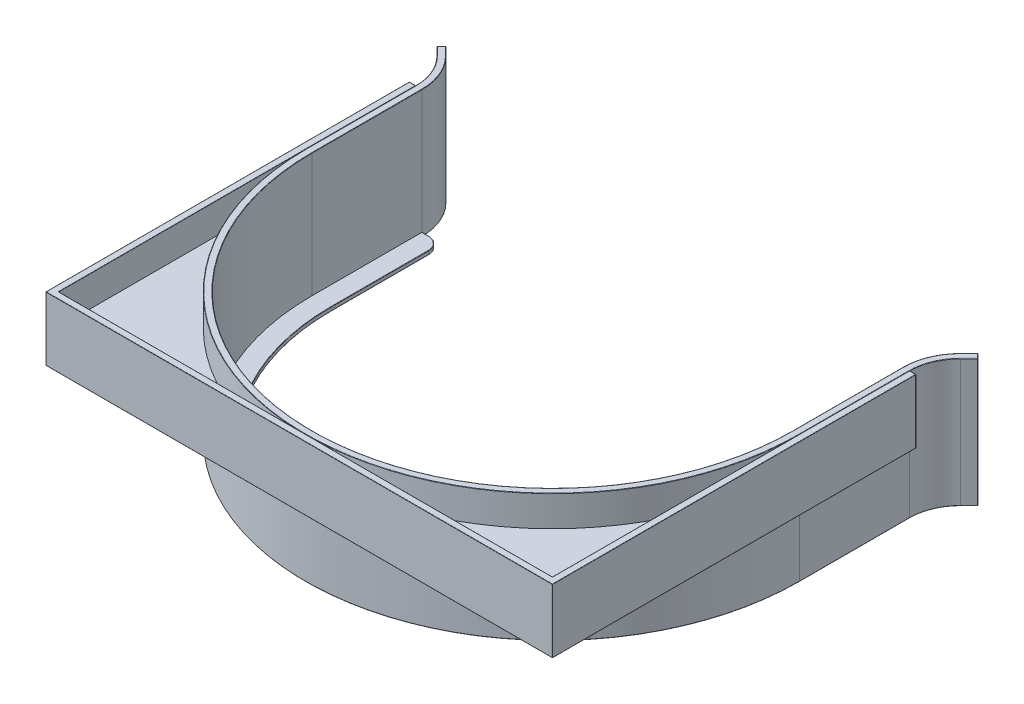
SolidWorks part; units mm, degrees
material "1060 Alloy"
ref_plane "Front Plane" through (0, 0, 0) normal (0, 0, 1) x (1, 0, 0)
ref_plane "Top Plane" through (0, 0, 0) normal (0, 1, 0) x (1, 0, 0)
ref_plane "Right Plane" through (0, 0, 0) normal (1, 0, 0) x (0, 0, -1)
sketch "Sketch1" plane through (0, 0, 0) normal (0, 1, 0) x (1, 0, 0)
  line L8 (193.5, 0) -> (188.5, 0)
  line L9 (-193.5, 0) -> (-188.5, 0)
  arc A0 (-188.5, 0) -> (188.5, 0) centre (0, 0) ccw
  arc A1 (-193.5, 0) -> (193.5, 0) centre (0, 0) ccw
  circle A2 centre (0, 0) radius 193.5 construction
  circle A3 centre (0, 0) radius 188.5 construction
  dimension "D1" = 377
  dimension "D2" = 5
extrude "Boss-Extrude1" add sketch "Sketch1" along normal blind 100 contours A1 L8 A0 L9 region at (0, 0, 189.1732)
sketch "Sketch2" plane through (0, 0, 0) normal (0, 1, 0) x (1, 0, 0)
  line L0 (-212.0355, 121.4645) -> (-205.2157, 114.6447)
  line L1 (-212.0355, 121.4645) -> (-208.5, 125)
  line L2 (-208.5, 125) -> (-201.6802, 118.1802)
  line L3 (-193.5, 86.3604) -> (-193.5, 0)
  line L4 (-188.5, 0) -> (-188.5, 86.3604)
  line L5 (-188.5, 0) -> (-193.5, 0)
  arc A0 (-205.2157, 114.6447) -> (-193.5, 86.3604) centre (-233.5, 86.3604) cw
  arc A2 (-201.6802, 118.1802) -> (-188.5, 86.3604) centre (-233.5, 86.3604) cw
  arc A5 (-193.5, 0) -> (193.5, 0) centre (0, 0) ccw construction
  dimension "D4" = 135
  dimension "D3" = 40
  dimension "D2" = 125
  dimension "D1" = 20
extrude "Boss-Extrude2" add sketch "Sketch2" along normal up to surface (100 mm away) up to face at (0, 100, 95.5)
mirror "Mirror1" about plane through (0, 0, 0) normal (1, 0, 0) of "Boss-Extrude2"
sketch "Sketch3" plane through (0, 0, 0) normal (0, 1, 0) x (1, 0, 0)
  line L0 (-188.5, 0) -> (-188.5, 86.3604)
  line L1 (188.5, 0) -> (188.5, 86.3604)
  line L2 (-188.5, 86.3604) -> (-173.5, 86.3604)
  line L3 (-173.5, 86.3604) -> (-173.5, 0)
  line L4 (188.5, 86.3604) -> (173.5, 86.3604)
  line L5 (173.5, 86.3604) -> (173.5, 0)
  arc A0 (-188.5, 0) -> (188.5, 0) centre (0, 0) ccw construction
  arc A1 (-188.5, 0) -> (188.5, 0) centre (0, 0) ccw
  arc A2 (-173.5, 0) -> (173.5, 0) centre (0, 0) ccw
  dimension "D1" = 347
extrude "Boss-Extrude3" add sketch "Sketch3" along normal blind 3
fillet "Fillet1" radius 10 2 edges at (-173.5, 1.5, -86.3604) (173.5, 1.5, -86.3604)
ref_plane "Plane1" through (0, 40, 0) normal (0, 1, 0) x (1, 0, 0)
ref_plane "Plane2" through (0, 100, 0) normal (0, 1, 0) x (1, 0, 0)
sketch "Sketch4" plane through (0, 100, 0) normal (0, 1, 0) x (1, 0, 0)
  line L0 (-193.5, 86.3604) -> (-193.5, -193.5)
  line L1 (-193.5, -193.5) -> (193.5, -193.5)
  line L2 (193.5, -193.5) -> (193.5, 86.3604)
  line L3 (-198.5, 86.3604) -> (-198.5, -198.5)
  line L4 (-198.5, -198.5) -> (198.5, -198.5)
  line L5 (198.5, -198.5) -> (198.5, 86.3604)
  line L6 (-193.5, 86.3604) -> (-198.5, 86.3604)
  line L7 (193.5, 86.3604) -> (198.5, 86.3604)
  arc A0 (-193.5, 0) -> (193.5, 0) centre (0, 0) ccw construction
  dimension "D1" = 5
extrude "Boss-Extrude4" add sketch "Sketch4" against normal blind 50 separate body
sketch "Sketch5" plane through (0, 0, 0) normal (1, 0, 0) x (0, 0, -1)
  line L0 (-198.5, 50) -> (-198.5, 100) construction
  line L1 (86.3604, 50) -> (86.3604, 100) construction
  line L2 (-198.5, 100) -> (86.3604, 100) construction
  point P0 (61.3604, 90)
  point P1 (-173.6396, 90)
  dimension "D1" = 25
  dimension "D2" = 235
  dimension "D3" = 10
ref_axis "Axis1" through (-228.7756, 90, 173.6396) along (1, 0, 0)
ref_axis "Axis2" through (-220.8647, 90, -61.3604) along (1, 0, 0)
ref_plane "Plane3" through (0, 75, 0) normal (0, 1, 0) x (1, 0, 0)
sketch "Sketch6" plane through (0, 75, 0) normal (0, 1, 0) x (1, 0, 0)
  line L0 (193.5, -193.5) -> (-193.5, -193.5) construction
  line L1 (-193.5, -193.5) -> (-193.5, 86.3604) construction
  line L2 (-48.1871, -193.5) -> (-193.5, -193.5)
  line L3 (-193.5, -193.5) -> (-193.5, -48.1871)
  arc A0 (-193.5, 0) -> (193.5, 0) centre (0, 0) ccw construction
  arc A1 (-187.5916, -47.4515) -> (-47.4515, -187.5916) centre (0, 0) ccw
  arc A2 (-47.4515, -187.5916) -> (-48.1871, -193.5) centre (-48.1871, -190.5) cw
  arc A3 (-187.5916, -47.4515) -> (-193.5, -48.1871) centre (-190.5, -48.1871) ccw
  dimension "D1" = 3
extrude "Boss-Extrude10" add sketch "Sketch6" along normal mid plane 2 separate body contours A1 A2 L2 L3 A3
mirror "Mirror3" about plane through (0, 0, 0) normal (1, 0, 0) of bodies 107
fillet "Fillet2" radius 0.3 47 edges at (-186, 0, -86.3604) (-176.4289, 0, -83.4315) (-173.5, 0, -38.1802) (0, 0, 173.5) (173.5, 0, -38.1802) (186, 0, -86.3604) (186, 3, -86.3604) (-186, 3, -86.3604) (-176.4289, 3, -83.4315) (-173.5, 3, -38.1802) (0, 3, 173.5) (173.5, 3, -38.1802) (-208.6256, 0, -118.0546) (-196.5448, 0, -101.6677) (-193.5, 0, -43.1802) (0, 0, 193.5) (193.5, 0, -43.1802) (208.6256, 100, -118.0546) (196.5448, 100, -101.6677) (193.5, 100, -43.1802) (0, 100, 193.5) (-193.5, 100, -43.1802) (-191.9254, 0, -103.5811) (191.9254, 0, -103.5811) (-205.0901, 100, -121.5901) (-191.9254, 100, -103.5811) (-188.5, 100, -43.1802) (205.0901, 100, -121.5901) (191.9254, 100, -103.5811) (188.5, 100, -43.1802) (176.4289, 0, -83.4315) (176.4289, 3, -83.4315) (196.5448, 0, -101.6677) (208.6256, 0, -118.0546) (210.2678, 0, -123.2322) (212.0355, 50, -121.4645) (210.2678, 100, -123.2322) (-208.6256, 100, -118.0546) (-196.5448, 100, -101.6677) (-210.2678, 100, -123.2322) (-212.0355, 50, -121.4645) (-210.2678, 0, -123.2322) (-205.0901, 0, -121.5901) (-208.5, 50, -125) (205.0901, 0, -121.5901) (208.5, 50, -125) (0, 100, 188.5)
fillet "Fillet3" radius 0.2 22 edges at (0, 100, 193.5) (193.5, 100, 53.5698) (196, 100, -86.3604) (-196, 100, -86.3604) (198.5, 75, -86.3604) (198.5, 100, 56.0698) (-193.5, 75, -86.3604) (-193.5, 75, 193.5) (-193.5, 100, 53.5698) (-198.5, 75, -86.3604) (-198.5, 100, 56.0698) (198.5, 75, 198.5) (-198.5, 75, 198.5) (0, 100, 198.5) (-198.5, 50, 56.0698) (0, 50, 198.5) (198.5, 50, 56.0698) (196, 50, -86.3604) (193.5, 50, 53.5698) (0, 50, 193.5) (-193.5, 50, 53.5698) (-196, 50, -86.3604)
